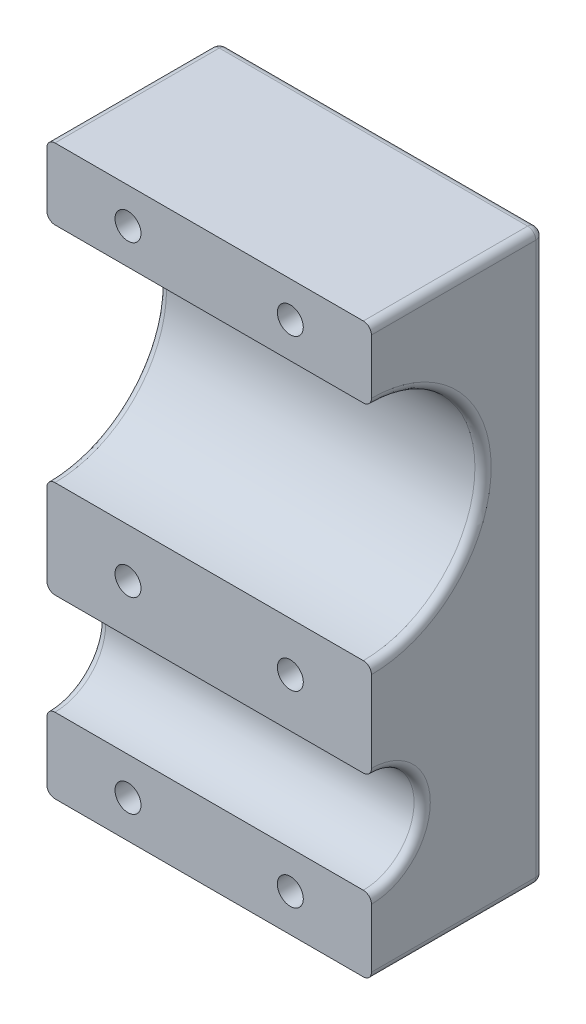
SolidWorks part; units mm, degrees
note: The reader was unsure of these and kept them because the rebuilt part matched: shared geometry of "Sketch5<3>".
ref_plane "Front Plane" through (0, 0, 0) normal (0, 0, 1) x (1, 0, 0)
ref_plane "Top Plane" through (0, 0, 0) normal (0, 1, 0) x (1, 0, 0)
ref_plane "Right Plane" through (0, 0, 0) normal (1, 0, 0) x (0, 0, -1)
sketch "Sketch1" plane through (0, 0, 0) normal (1, 0, 0) x (0, 0, -1)
  line L1 (0, 0) -> (53.975, 0)
  line L2 (0, 0) -> (0, 88.9)
  line L3 (0, 88.9) -> (53.975, 88.9)
  line L4 (53.975, 0) -> (53.975, 88.9)
  circle A0 centre (26.9875, 19.685) radius 7.9375
  circle A1 centre (26.9875, 60.325) radius 17.4625
  point P11 (26.9875, 88.9)
  dimension "D1" = 15.875
  dimension "D2" = 34.925
  dimension "D5" = 40.64
  dimension "D3" = 53.975
  dimension "D4" = 88.9
  dimension "D6" = 28.575
extrude "Boss-Extrude1" add sketch "Sketch1" along normal blind 50.8 contours A1 | A0 | L4 L3 L2 L1
sketch "Sketch5" plane through (0, 0, 0) normal (0, 0, 1) x (1, 0, 0)
  circle A0 centre (38.1, 35.2425) radius 2.032
  circle A1 centre (38.1, 35.2425) radius 3.5
  circle A2 centre (12.7, 83.3438) radius 2.032
  circle A3 centre (12.7, 83.3438) radius 3.5
  circle A4 centre (38.1, 83.3438) radius 2.032
  circle A5 centre (38.1, 83.3438) radius 3.5
  circle A6 centre (12.7, 35.2425) radius 2.032
  circle A7 centre (12.7, 35.2425) radius 3.5
  circle A8 centre (38.1, 5.8737) radius 2.032
  circle A9 centre (38.1, 5.8737) radius 3.5
  circle A10 centre (12.7, 5.8737) radius 2.032
  circle A11 centre (12.7, 5.8737) radius 3.5
  dimension "D3" = 4.064
  dimension "D4" = 4.064
  dimension "D5" = 4.064
  dimension "D6" = 4.064
  dimension "D7" = 4.064
  dimension "D8" = 4.064
  dimension "D1" = 25.4
  dimension "D2" = 12.7
extrude "Cut-Extrude1" cut sketch "Sketch5" against normal through all contours A2 | A6 | A4 | A0 | A10 | A8
extrude "Cut-Extrude2" cut sketch "Sketch5<3>" against normal blind 4.064 contours A3 | A5 | A1 | A7 | A11 | A9
sketch "Sketch5<3>" plane through (0, 0, 0) normal (0, 0, 1) x (1, 0, 0) same geometry as "Sketch5"
sketch "Sketch6" plane through (0, 0, -53.975) normal (0, 0, -1) x (-1, 0, 0)
  line L1 (-8.636, 83.3438) -> (-10.668, 86.8633)
  line L2 (-10.668, 86.8633) -> (-14.732, 86.8633)
  line L3 (-14.732, 86.8633) -> (-16.764, 83.3438)
  line L4 (-16.764, 83.3438) -> (-14.732, 79.8242)
  line L5 (-14.732, 79.8242) -> (-10.668, 79.8242)
  line L6 (-10.668, 79.8242) -> (-8.636, 83.3438)
  line L7 (-34.036, 83.3438) -> (-36.068, 86.8633)
  line L8 (-36.068, 86.8633) -> (-40.132, 86.8633)
  line L9 (-40.132, 86.8633) -> (-42.164, 83.3438)
  line L10 (-42.164, 83.3438) -> (-40.132, 79.8242)
  line L11 (-40.132, 79.8242) -> (-36.068, 79.8242)
  line L24 (-36.068, 79.8242) -> (-34.036, 83.3438)
  line L25 (-34.036, 35.2425) -> (-36.068, 38.762)
  line L26 (-36.068, 38.762) -> (-40.132, 38.762)
  line L39 (-40.132, 38.762) -> (-42.164, 35.2425)
  line L40 (-42.164, 35.2425) -> (-40.132, 31.723)
  line L41 (-40.132, 31.723) -> (-36.068, 31.723)
  line L54 (-36.068, 31.723) -> (-34.036, 35.2425)
  line L55 (-8.636, 35.2425) -> (-10.668, 38.762)
  line L56 (-10.668, 38.762) -> (-14.732, 38.762)
  line L69 (-14.732, 38.762) -> (-16.764, 35.2425)
  line L70 (-16.764, 35.2425) -> (-14.732, 31.723)
  line L71 (-14.732, 31.723) -> (-10.668, 31.723)
  line L84 (-10.668, 31.723) -> (-8.636, 35.2425)
  line L85 (-8.636, 5.8737) -> (-10.668, 9.3933)
  line L86 (-10.668, 9.3933) -> (-14.732, 9.3933)
  line L99 (-14.732, 9.3933) -> (-16.764, 5.8737)
  line L100 (-16.764, 5.8737) -> (-14.732, 2.3542)
  line L101 (-14.732, 2.3542) -> (-10.668, 2.3542)
  line L102 (-10.668, 2.3542) -> (-8.636, 5.8737)
  line L103 (-34.036, 5.8737) -> (-36.068, 9.3933)
  line L104 (-36.068, 9.3933) -> (-40.132, 9.3933)
  line L105 (-40.132, 9.3933) -> (-42.164, 5.8737)
  line L106 (-42.164, 5.8737) -> (-40.132, 2.3542)
  line L107 (-40.132, 2.3542) -> (-36.068, 2.3542)
  line L108 (-36.068, 2.3542) -> (-34.036, 5.8737)
  circle A7 centre (-12.7, 83.3438) radius 3.5195 construction
  circle A8 centre (-38.1, 83.3438) radius 3.5195 construction
  circle A9 centre (-38.1, 35.2425) radius 3.5195 construction
  circle A10 centre (-12.7, 35.2425) radius 3.5195 construction
  circle A11 centre (-12.7, 5.8737) radius 3.5195 construction
  circle A12 centre (-38.1, 5.8737) radius 3.5195 construction
  circle M1 centre (-12.7, 5.8737) radius 2.032
  circle M2 centre (-38.1, 35.2425) radius 2.032
  circle M3 centre (-38.1, 83.3438) radius 2.032
  circle M4 centre (-12.7, 35.2425) radius 2.032
  circle M5 centre (-38.1, 5.8737) radius 2.032
  dimension "D1" = 4.064
  dimension "D2" = 4.064
  dimension "D3" = 4.064
  dimension "D4" = 4.064
  dimension "D5" = 4.064
  dimension "D6" = 4.064
extrude "Cut-Extrude3" cut sketch "Sketch6" against normal blind 2.54 contours L11 L24 L7 L8 L9 L10 M3 | L41 L54 L25 L26 L39 L40 M2 | L71 L84 L55 L56 L69 L70 M4 | L107 L108 L103 L104 L105 L106 M5 | L101 L102 L85 L86 L99 L100 M1
fillet "Fillet1" radius 1.27 16 edges at (25.4, 0, 0) (25.4, 0, -53.975) (50.8, 19.685, -34.925) (0, 19.685, -34.925) (0, 0, -26.9875) (50.8, 0, -26.9875) (50.8, 60.325, -44.45) (0, 60.325, -44.45) (0, 44.45, 0) (50.8, 44.45, 0) (0, 44.45, -53.975) (50.8, 44.45, -53.975) (25.4, 88.9, 0) (0, 88.9, -26.9875) (50.8, 88.9, -26.9875) (25.4, 88.9, -53.975)
ref_plane "Plane1" through (0, 0, -26.9875) normal (0, 0, 1) x (1, 0, 0)
other "SurfaceCut1" flip cut yes
